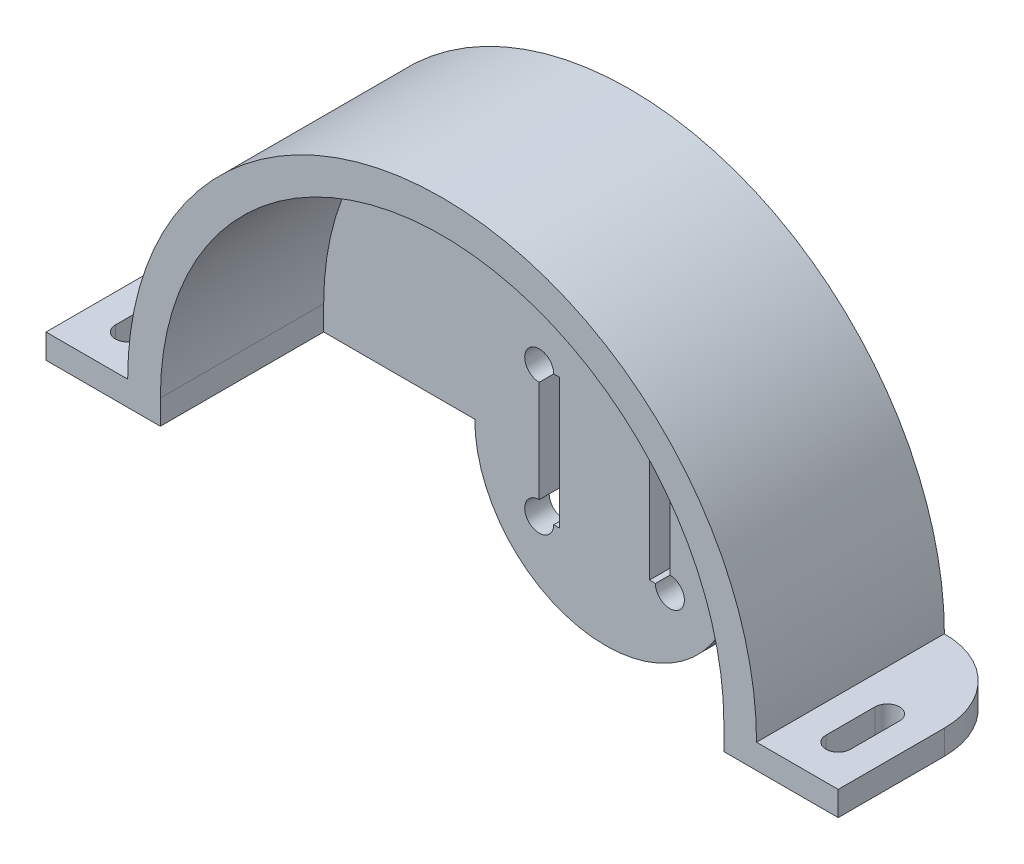
SolidWorks part; units mm, degrees
ref_plane "Plan de face" through (0, 0, 0) normal (0, 0, 1) x (1, 0, 0)
ref_plane "Plan de dessus" through (0, 0, 0) normal (0, 1, 0) x (1, 0, 0)
ref_plane "Plan de droite" through (0, 0, 0) normal (1, 0, 0) x (0, 0, -1)
sketch "Esquisse1" plane through (0, 0, 0) normal (0, 0, 1) x (1, 0, 0)
  line L0 (0, 0) -> (10, 0) construction
  line L2 (0, 0) -> (10, 0)
  line L3 (0, 0) -> (0, -3)
  line L4 (0, -3) -> (97, -3)
  line L5 (97, 0) -> (97, -3)
  line L6 (87, 0) -> (97, 0)
  arc A1 (10, 0) -> (87, 0) centre (48.5, 0) cw
  dimension "D1" = 10
  dimension "D4" = 38.5
  dimension "D2" = 3
  dimension "D3" = 10
  dimension "D5" = 97
extrude "Boss.-Extru.1" add sketch "Esquisse1" along normal blind 3 contours A1 L2 L3 L4 L5 L6 region at (48.5, 14.3579, 0)
sketch "Esquisse2" plane through (0, 0, 3) normal (0, 0, 1) x (1, 0, 0)
  line L5 (0, -3) -> (97, -3) construction
  line L10 (0, 0) -> (14, 0)
  line L11 (0, 0) -> (0, -3)
  line L12 (0, -3) -> (14, -3)
  line L13 (14, 0) -> (14, -3)
  line L15 (97, 0) -> (83, 0)
  line L16 (97, 0) -> (97, -3)
  line L17 (97, -3) -> (83, -3)
  line L18 (83, 0) -> (83, -3)
  arc A0 (14, 0) -> (83, 0) centre (48.5, 0) cw
  arc A2 (10, 0) -> (87, 0) centre (48.5, 0) cw
  line M1 (97, -3) -> (97, 0)
  arc M3 (87, 0) -> (10, 0) centre (48.5, 0) ccw
  line M4 (10, 0) -> (0, 0)
  line M5 (0, 0) -> (0, -3)
  line M6 (0, -3) -> (97, -3)
  line M26 (97, 0) -> (87, 0)
  dimension "D1" = 14
  dimension "D2" = 14
extrude "Boss.-Extru.2" add sketch "Esquisse2" along normal blind 20 contours L13 L10 M4 M5 M6 | L10 L15 M3 | L15 L18 M6 M1 M26 region at (7, -1.5, 3) region at (48.5, 37.6391, 3) region at (90, -1.5, 3)
sketch "Esquisse4" plane through (0, 0, 0) normal (0, 0, -1) x (-1, 0, 0)
  line L3 (0, -3) -> (-97, -3) construction
  line L4 (-64.5, -3) -> (-32.5, -3)
  arc A2 (-64.5, -3) -> (-32.5, -3) centre (-48.5, -3) ccw
  dimension "D1" = 32
extrude "Boss.-Extru.3" add sketch "Esquisse4" against normal blind 3
sketch "Esquisse7" plane through (0, 0, 0) normal (0, 1, 0) x (1, 0, 0)
  line L0 (5, -18) -> (5, -12) construction
  line L1 (97, -23) -> (87, -23) construction
  line L2 (3.5, -18) -> (3.5, -12)
  line L3 (97, -23) -> (97, 0) construction
  line L4 (0, -23) -> (0, 0) construction
  line L6 (6.5, -18) -> (6.5, -12)
  line L7 (0, -23) -> (10, -23) construction
  line L8 (92, -18) -> (92, -12) construction
  line L9 (90.5, -18) -> (90.5, -12)
  line L10 (93.5, -18) -> (93.5, -12)
  arc A2 (3.5, -18) -> (6.5, -18) centre (5, -18) ccw
  arc A3 (6.5, -12) -> (3.5, -12) centre (5, -12) ccw
  arc A4 (90.5, -18) -> (93.5, -18) centre (92, -18) ccw
  arc A5 (93.5, -12) -> (90.5, -12) centre (92, -12) ccw
  point P2 (5, -15)
  point P18 (92, -15)
  dimension "D5" = 5
  dimension "D7" = 1.5
  dimension "D6" = 1.5
  dimension "D1" = 5
  dimension "D2" = 5
  dimension "D3" = 5
  dimension "D8" = 6
  dimension "D9" = 6
extrude "Enlèv. mat.-Extru.2" cut sketch "Esquisse7" against normal blind 10
sketch "Esquisse9" plane through (0, 0, 3) normal (0, 0, 1) x (1, 0, 0)
  line L0 (42.3901, 1.745) -> (42.3901, 0.245) construction
  line L1 (40.3901, 6.64) -> (42.8901, 6.64)
  line L2 (40.3901, 6.64) -> (40.3901, -9.36)
  line L3 (40.3901, -9.36) -> (42.8901, -9.36)
  line L4 (42.8901, 6.64) -> (42.8901, -9.36)
  line L5 (56.3901, -9.36) -> (53.8901, -9.36)
  line L6 (56.3901, -9.36) -> (56.3901, 6.64)
  line L7 (56.3901, 6.64) -> (53.8901, 6.64)
  line L8 (53.8901, -9.36) -> (53.8901, 6.64)
  line L9 (54.3901, 1.985) -> (54.3901, 3.485) construction
  circle A0 centre (40.3901, 6.64) radius 1.775
  circle A1 centre (56.3901, 6.64) radius 1.775
  circle A2 centre (40.3901, -9.36) radius 1.775
  circle A3 centre (56.3901, -9.36) radius 1.775
  dimension "D1" = 0.5
  dimension "D2" = 0.5
extrude "Enlèv. mat.-Extru.3" cut sketch "Esquisse9" against normal blind 10 contours L1 A0 L2 | L2 A0 L1 | A2 L3 L4 L1 A0 L2 | L6 A1 L7 | L7 A1 L6 | L5 A3 L6 | L6 A3 L5 | L2 A2 L3 | L3 A2 L2 | L8 L7 L6 L5 region at (40.139, 6.8911, 3) region at (41.1435, 5.8867, 3) region at (41.7103, -1.36, 3) region at (41.1435, -8.6067, 3) region at (40.139, -9.6111, 3) region at (56.6412, -9.6111, 3) region at (55.6368, -8.6067, 3) region at (55.6368, 5.8867, 3) region at (56.6412, 6.8911, 3)
fillet "Congé1" radius 10 1 edges at (97, -1.5, 0)
fillet "Congé2" radius 10 1 edges at (0, -1.5, 0)
